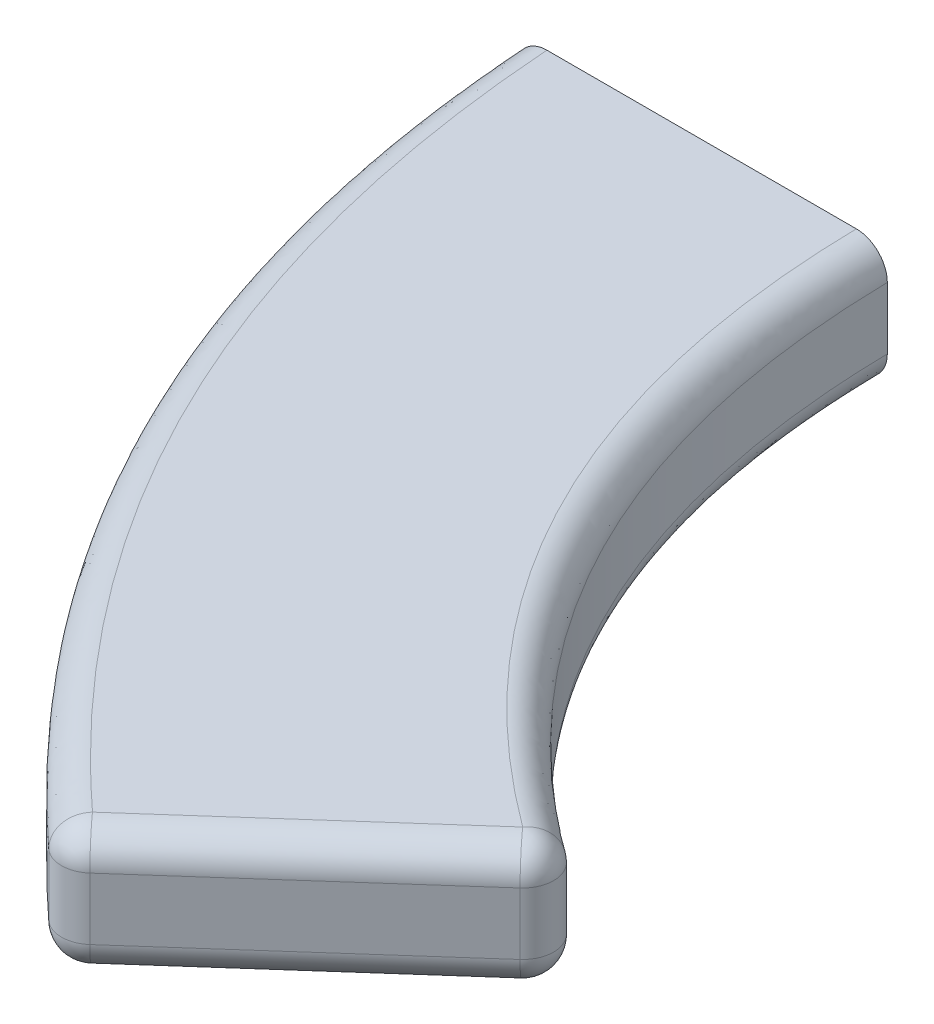
SolidWorks part; units mm, degrees
ref_plane "Front Plane" through (0, 0, 0) normal (0, 0, 1) x (1, 0, 0)
ref_plane "Top Plane" through (0, 0, 0) normal (0, 1, 0) x (1, 0, 0)
ref_plane "Right Plane" through (0, 0, 0) normal (1, 0, 0) x (0, 0, -1)
sketch "Sketch1" plane through (0, 0, 0) normal (0, 1, 0) x (1, 0, 0)
  line L0 (0, 0) -> (60, 0)
  line L1 (74.8728, -150) -> (119.7666, -110.1936)
  spline S0 degree 2 poles (0, 0) (6.0602, -88.9934) (74.8728, -150) knots 0 0 0 1 1 1
  spline S1 degree 2 poles (60, 0) (61.1692, -70.2582) (119.7666, -110.1936) knots 0 0 0 1 1 1
  point P7 (128.5734, -113.7163)
  point P8 (74.2647, -60.2883)
  point P9 (0, 0)
  point P10 (119.7666, -110.1936)
  dimension "D1" = 60
  dimension "D2" = 60
  dimension "D3" = 150
  dimension "D4" = 60
extrude "Boss-Extrude1" add sketch "Sketch1" along normal blind 20
fillet "Fillet1" radius 5 8 edges at (74.8728, 10, 150) (97.3197, 20, 130.0968) (119.7666, 10, 110.1936) (97.3197, 0, 130.0968)
